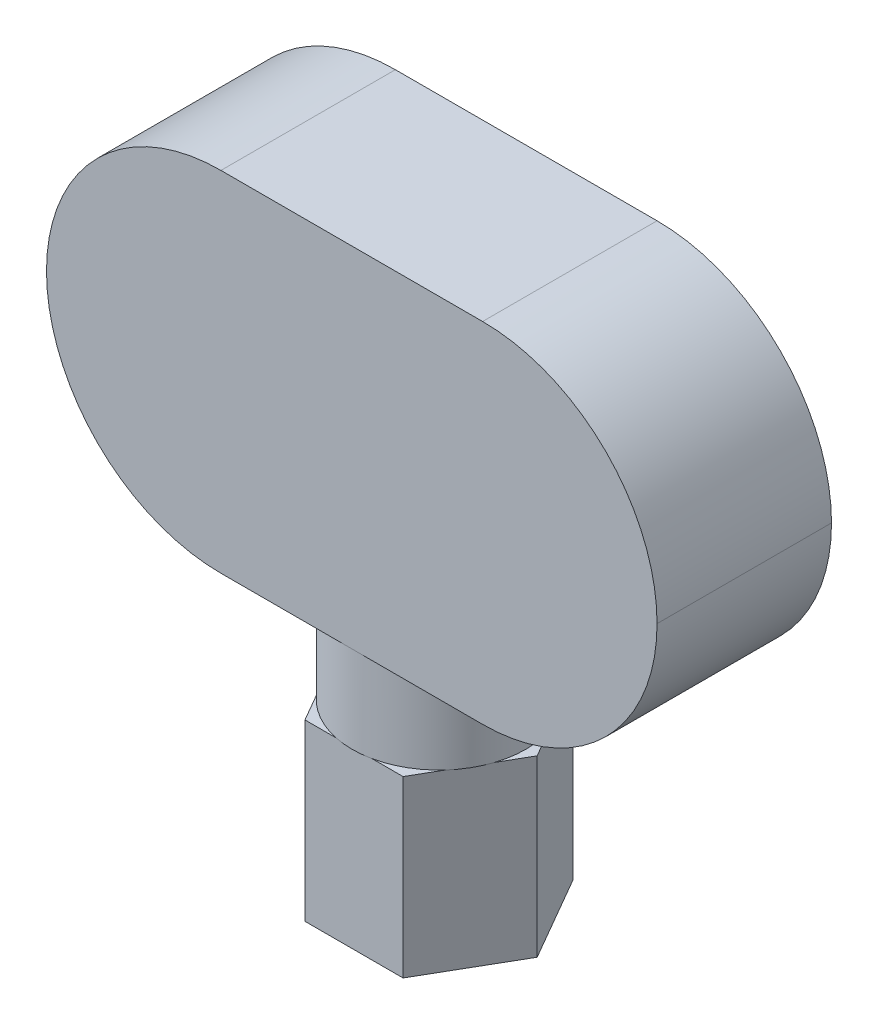
SolidWorks part; units mm, degrees
ref_plane "Front Plane" through (0, 0, 0) normal (0, 0, 1) x (1, 0, 0)
ref_plane "Top Plane" through (0, 0, 0) normal (0, 1, 0) x (1, 0, 0)
ref_plane "Right Plane" through (0, 0, 0) normal (1, 0, 0) x (0, 0, -1)
sketch "Sketch1" plane through (0, 0, 0) normal (0, 1, 0) x (1, 0, 0)
  line L1 (1.125, 1.9486) -> (-1.125, 1.9486)
  line L2 (-1.125, 1.9486) -> (-2.25, 0)
  line L3 (-2.25, 0) -> (-1.125, -1.9486)
  line L4 (-1.125, -1.9486) -> (1.125, -1.9486)
  line L5 (1.125, -1.9486) -> (2.25, 0)
  line L6 (2.25, 0) -> (1.125, 1.9486)
  circle A0 centre (0, 0) radius 1.9486 construction
  dimension "D1" = 2.25
extrude "Boss-Extrude1" add sketch "Sketch1" along normal blind 4
sketch "Sketch3" plane through (0, 4, 0) normal (0, 1, 0) x (1, 0, 0)
  circle A0 centre (0, 0) radius 1.9919
extrude "Boss-Extrude3" add sketch "Sketch3" along normal blind 2
sketch "Sketch2" plane through (0, 6, 0) normal (0, 1, 0) x (1, 0, 0)
  line L1 (-7, 2) -> (7, 2)
  line L2 (-7, 2) -> (-7, -2)
  line L3 (-7, -2) -> (7, -2)
  line L4 (7, 2) -> (7, -2)
  line L5 (-7, 2) -> (7, -2) construction
  line L6 (-7, -2) -> (7, 2) construction
  point P0 (0, 0)
  dimension "D1" = 4
  dimension "D2" = 14
extrude "Boss-Extrude2" add sketch "Sketch2" along normal blind 8
fillet "Fillet1" radius 4 4 edges at (7, 6, 0) (7, 14, 0) (-7, 6, 0) (-7, 14, 0)
